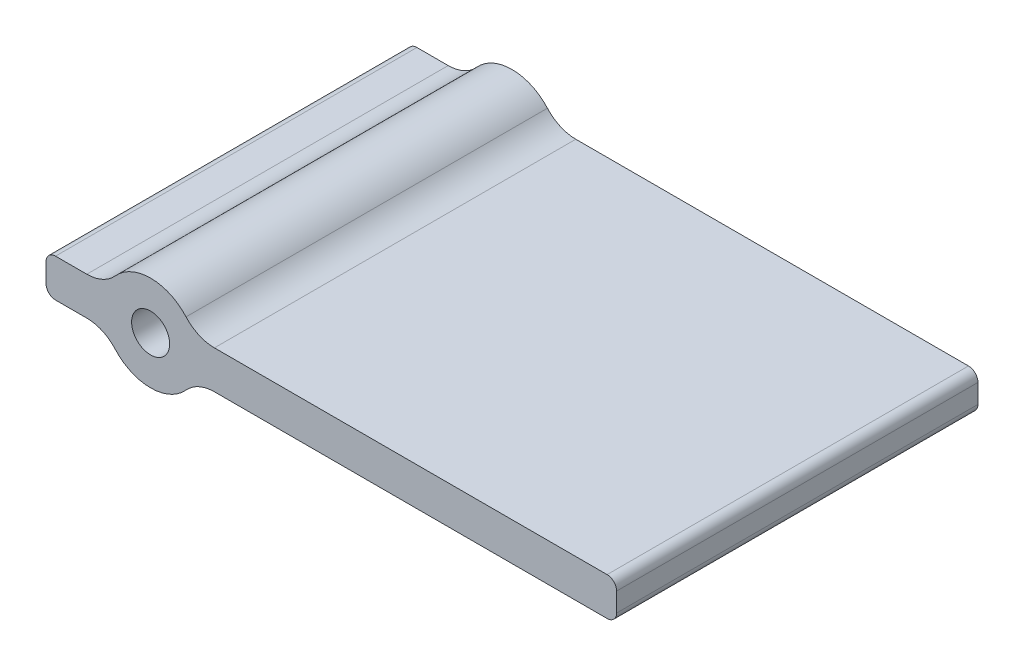
SolidWorks part; units mm, degrees
ref_plane "Front Plane" through (0, 0, 0) normal (0, 0, 1) x (1, 0, 0)
ref_plane "Top Plane" through (0, 0, 0) normal (0, 1, 0) x (1, 0, 0)
ref_plane "Right Plane" through (0, 0, 0) normal (1, 0, 0) x (0, 0, -1)
sketch "Sketch1" plane through (0, 0, 0) normal (0, 0, 1) x (1, 0, 0)
  line L0 (-943.663, 304.3873) -> (-956.6481, 304.3873) construction
  line L1 (-943.663, 304.3873) -> (-916.4663, 304.3873) construction
  line L3 (-948.663, 303.3873) -> (-947.0171, 303.3873)
  line L4 (-949.163, 303.8873) -> (-949.163, 304.8873)
  line L5 (-948.663, 305.3873) -> (-947.0171, 305.3873)
  line L6 (-919.163, 303.8873) -> (-919.163, 304.8873)
  line L7 (-949.163, 303.3873) -> (-919.163, 305.3873) construction
  line L8 (-949.163, 305.3873) -> (-919.163, 303.3873) construction
  line L9 (-940.3089, 305.3873) -> (-919.663, 305.3873)
  line L10 (-940.3089, 303.3873) -> (-919.663, 303.3873)
  arc A0 (-945.5264, 302.7207) -> (-941.7996, 302.7207) centre (-943.663, 304.3873) ccw
  arc A1 (-941.7996, 306.054) -> (-945.5264, 306.054) centre (-943.663, 304.3873) ccw
  arc A2 (-945.5264, 302.7207) -> (-947.0171, 303.3873) centre (-947.0171, 301.3873) ccw
  arc A3 (-941.7996, 302.7207) -> (-940.3089, 303.3873) centre (-940.3089, 301.3873) cw
  arc A4 (-941.7996, 306.054) -> (-940.3089, 305.3873) centre (-940.3089, 307.3873) ccw
  arc A5 (-947.0171, 305.3873) -> (-945.5264, 306.054) centre (-947.0171, 307.3873) ccw
  arc A6 (-948.663, 303.3873) -> (-949.163, 303.8873) centre (-948.663, 303.8873) cw
  circle A7 centre (-943.663, 304.3873) radius 1
  arc A8 (-949.163, 304.8873) -> (-948.663, 305.3873) centre (-948.663, 304.8873) cw
  arc A9 (-919.663, 303.3873) -> (-919.163, 303.8873) centre (-919.663, 303.8873) ccw
  arc A10 (-919.663, 305.3873) -> (-919.163, 304.8873) centre (-919.663, 304.8873) cw
  point P3 (-934.163, 304.3873)
  point P19 (-941.3717, 303.3873)
  point P22 (-941.3717, 305.3873)
  dimension "D4" = 5
  dimension "D5" = 2
  dimension "D6" = 0.5
  dimension "D7" = 0.5
  dimension "D1" = 2
  dimension "D2" = 5.5
  dimension "D3" = 30
extrude "Boss-Extrude1" add sketch "Sketch1" along normal blind 9.5 and the other way blind 9.5
